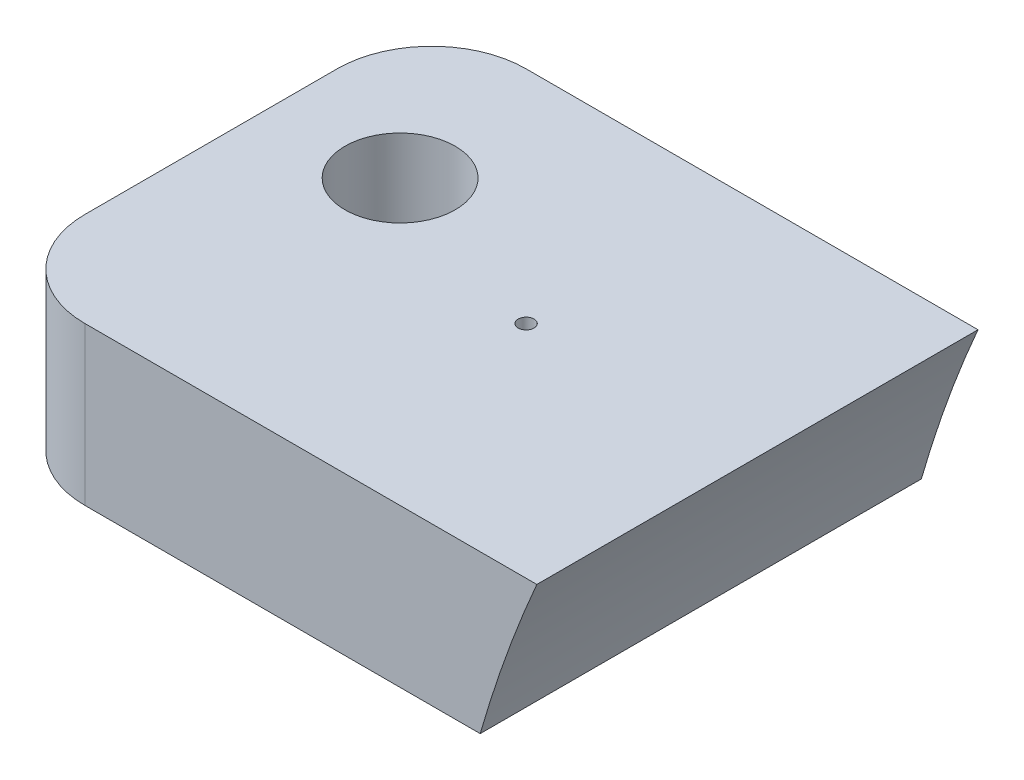
SolidWorks part; units mm, degrees
material "Acrylic (Medium-high impact)"
ref_plane "Front Plane" through (0, 0, 0) normal (0, 0, 1) x (1, 0, 0)
ref_plane "Top Plane" through (0, 0, 0) normal (0, 1, 0) x (1, 0, 0)
ref_plane "Right Plane" through (0, 0, 0) normal (1, 0, 0) x (0, 0, -1)
ref_axis "Axis1" through (0, 0, -12.1) along (0, 0, 1)
sketch "Sketch1" plane through (0, 0, 0) normal (0, 0, 1) x (1, 0, 0)
  circle A0 centre (0, 0) radius 38
  circle A1 centre (0, 0) radius 40
  dimension "D1" = 76
  dimension "D2" = 2
extrude "Boss-Extrude1" add sketch "Sketch1" along normal blind 200
ref_plane "Plane1" through (0, 0, 180) normal (0, 0, 1) x (1, 0, 0)
sketch "Sketch2" plane through (0, 0, 180) normal (0, 0, 1) x (1, 0, 0)
  circle A0 centre (0, 0) radius 40 construction
  circle A1 centre (0, 0) radius 40
extrude "Boss-Extrude2" add sketch "Sketch2" along normal blind 2
sketch "Sketch3" plane through (0, 0, 0) normal (0, 0, -1) x (-1, 0, 0)
  line L0 (-24, -32) -> (-72, -32)
  line L1 (-72, -32) -> (-72, -30)
  line L2 (-72, -30) -> (-26.4575, -30)
  line L3 (-24, 32) -> (-72, 32)
  line L4 (-72, 30) -> (-26.4575, 30)
  line L5 (-72, 32) -> (-72, 30)
  line L6 (-40, -15.2942) -> (-40, 13.2229) construction
  line L8 (0, 0) -> (-59.0266, 0) construction
  circle A1 centre (0, 0) radius 40 construction
  arc A2 (-24, 32) -> (-26.4575, 30) centre (0, 0) ccw
  arc A3 (-26.4575, -30) -> (-24, -32) centre (0, 0) ccw
  dimension "D1" = 60
  dimension "D2" = 2
  dimension "D3" = 32
extrude "Boss-Extrude3" add sketch "Sketch3" against normal blind 107
sketch "Sketch4" plane through (0, 0, 107) normal (0, 0, 1) x (1, 0, 0)
  line L2 (72, -32) -> (24, -32) construction
  line L3 (24, 32) -> (72, 32) construction
  line L4 (72, -32) -> (24, -32)
  line L5 (24, 32) -> (72, 32)
  line L6 (72, -32) -> (72, 32)
  circle A0 centre (0, 0) radius 40 construction
  arc A2 (24, -32) -> (24, 32) centre (0, 0) ccw
extrude "Boss-Extrude4" add sketch "Sketch4" along normal blind 2
sketch "Sketch5" plane through (0, 32, 0) normal (0, 1, 0) x (1, 0, 0)
  circle A5 centre (43.5, -102.5) radius 1.75 construction
  circle A6 centre (43.5, -102.5) radius 1.75
  circle A7 centre (43.5, -3.5) radius 1.75 construction
  circle A8 centre (43.5, -3.5) radius 1.75
  circle A9 centre (68.5, -78) radius 1.75 construction
  circle A10 centre (68.5, -78) radius 1.75
extrude "Cut-Extrude1" cut sketch "Sketch5" against normal through all
ref_plane "Plane2" through (0, 0, 0) normal (-0.7071, 0.7071, 0) x (0, 0, 1)
sketch "Sketch6" plane through (0, 0, 0) normal (-0.7071, 0.7071, 0) x (0, 0, 1)
  line L0 (200, -40) -> (200, 40) construction
  line L1 (200, -40) -> (200, 40) construction
  circle A0 centre (187, 0) radius 4
  dimension "D1" = 8
  dimension "D2" = 13
extrude "Cut-Extrude2" cut sketch "Sketch6" against normal up to next and the other way up to next
pattern_circular "CirPattern1" count 2 every 90 about axis through (0, 0, -12.1) along (0, 0, 1) of "Cut-Extrude2"
ref_plane "Plane3" through (-54, 0, 0) normal (1, 0, 0) x (0, 0, -1)
sketch "Sketch7" plane through (-54, 0, 0) normal (1, 0, 0) x (0, 0, -1)
  line L0 (0, 0) -> (-33.0452, 0) construction
  line L1 (-14, -11) -> (0, -11)
  line L2 (-14, -11) -> (-14, -16)
  line L3 (-14, -16) -> (0, -16)
  line L4 (0, -11) -> (0, -16)
  line L5 (0, -40) -> (0, 40) construction
  line L6 (0, 11) -> (0, 16)
  line L7 (-14, 16) -> (0, 16)
  line L8 (-14, 11) -> (-14, 16)
  line L9 (-14, 11) -> (0, 11)
  dimension "D1" = 5
  dimension "D2" = 14
  dimension "D3" = 22
extrude "Boss-Extrude5" add sketch "Sketch7" along normal up to surface (15.5422 mm away) up to face at (25.3934, 30.9059, 187.8976)
sketch "Sketch8" plane through (0, -16, 0) normal (0, -1, 0) x (1, 0, 0)
  line L1 (0, 0) -> (0, -11.8897) construction
  line L7 (-36.6606, 0) -> (-54, 0) construction
  circle A0 centre (-50, 5) radius 1.75
  dimension "D3" = 3.5
  dimension "D1" = 50
  dimension "D2" = 5
extrude "Cut-Extrude3" cut sketch "Sketch8" against normal up to surface (32 mm away) up to face at (-45.3303, 16, 7)
fillet "Fillet1" radius 3 4 edges at (-54, 13.5, 0) (-54, -13.5, 0) (-54, -13.5, 14) (-54, 13.5, 14)
sketch "Sketch9" plane through (0, 11, 0) normal (0, -1, 0) x (1, 0, 0)
  circle A0 centre (-44, 7) radius 0.25
  circle A1 centre (-50, 5) radius 1.75 construction
  dimension "D1" = 6
  dimension "D2" = 2
  dimension "D3" = 0.5
extrude "Cut-Extrude4" cut sketch "Sketch9" against normal up to next
sketch "Sketch10" plane through (0, 0, 0) normal (0, 0, -1) x (-1, 0, 0)
  line L0 (-10, 38.7298) -> (-10, 36.6606)
  line L2 (10, 38.7298) -> (10, 36.6606)
  line L3 (-10, -36.6606) -> (-10, -38.7298)
  line L4 (10, -36.6606) -> (10, -38.7298)
  line L5 (-10, 36.6606) -> (10, 36.6606) construction
  line L6 (0, 36.6606) -> (0, 0) construction
  circle A0 centre (0, 0) radius 38 construction
  arc A1 (36.6606, 16) -> (-24, 32) centre (0, 0) ccw construction
  arc A2 (-10, -36.6606) -> (10, -36.6606) centre (0, 0) ccw
  arc A3 (36.6606, 16) -> (-10, 38.7298) centre (0, 0) ccw
  arc A4 (10, 36.6606) -> (-10, 36.6606) centre (0, 0) ccw
  arc A5 (-24, -32) -> (36.6606, -16) centre (0, 0) ccw construction
  arc A6 (-10, -38.7298) -> (36.6606, -16) centre (0, 0) ccw
  arc M9 (36.6606, 16) -> (-24, 32) centre (0, 0) ccw
  arc M17 (-24, -32) -> (36.6606, -16) centre (0, 0) ccw
  circle M22 centre (0, 0) radius 38
  dimension "D1" = 20
extrude "Boss-Extrude6" add sketch "Sketch10" along normal blind 2 contours L4 L3 M22 M17 | L2 L0 M9 M22 region at (0, 38.5641, 0) region at (0, -38.5641, 0)
sketch "Sketch11" plane through (0, 0, 200) normal (0, 0, 1) x (1, 0, 0)
  arc A0 (14.0627, 37.4465) -> (-39.7688, 4.2946) centre (0, 0) ccw
  arc A1 (66.7652, -101.1185) -> (14.0627, 37.4465) centre (111.4844, -4.8047) ccw
  arc A2 (-39.7688, 4.2946) -> (66.7652, -101.1185) centre (-2.4633, -64.5432) ccw
extrude "Cut-Extrude5" cut sketch "Sketch11" against normal up to next
